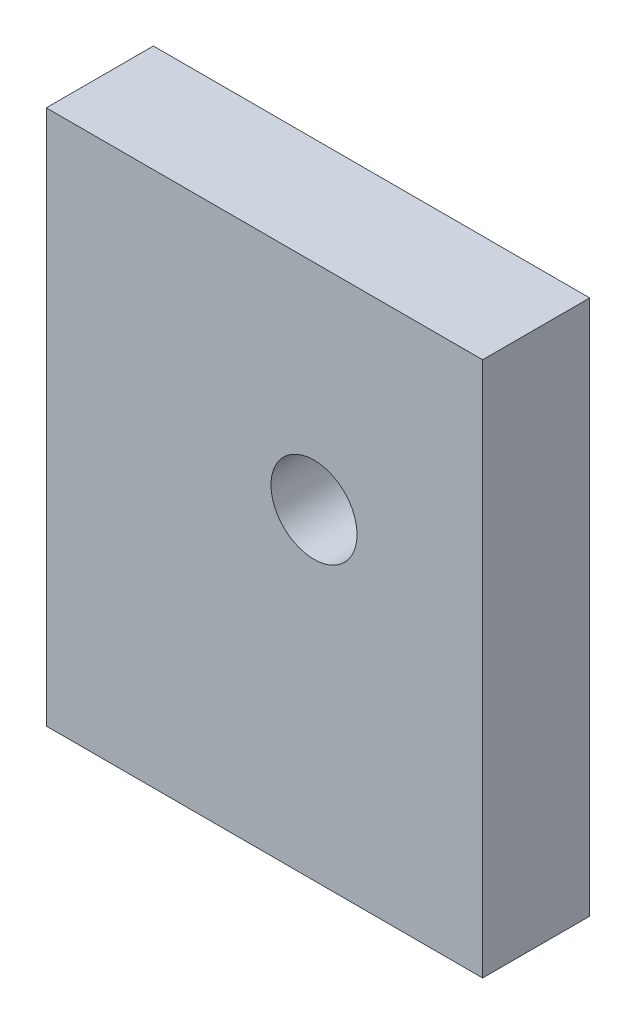
SolidWorks part; units mm, degrees
ref_plane "Front Plane" through (0, 0, 0) normal (0, 0, 1) x (1, 0, 0)
ref_plane "Top Plane" through (0, 0, 0) normal (0, 1, 0) x (1, 0, 0)
ref_plane "Right Plane" through (0, 0, 0) normal (1, 0, 0) x (0, 0, -1)
sketch "Sketch1" plane through (0, 0, 0) normal (0, 0, 1) x (1, 0, 0)
  line L0 (-48.4788, 51.0759) -> (-22.6038, 51.0759)
  line L1 (-22.6038, 51.0759) -> (-22.6038, 19.3259)
  line L2 (-48.4788, 51.0759) -> (-48.4788, 19.3259)
  line L3 (-48.4788, 19.3259) -> (-22.6038, 19.3259)
  circle A0 centre (-32.6038, 38.3759) radius 2.551
  dimension "D1" = 5.102
  dimension "D2" = 10
extrude "Boss-Extrude1" add sketch "Sketch1" along normal blind 6.35 contours L0 L1 L3 L2
extrude "Cut-Extrude3" cut sketch "Sketch1<4>" along normal through all flip side to cut
sketch "Sketch1<4>" plane through (0, 0, 0) normal (0, 0, 1) x (1, 0, 0) same geometry as "Sketch1"
